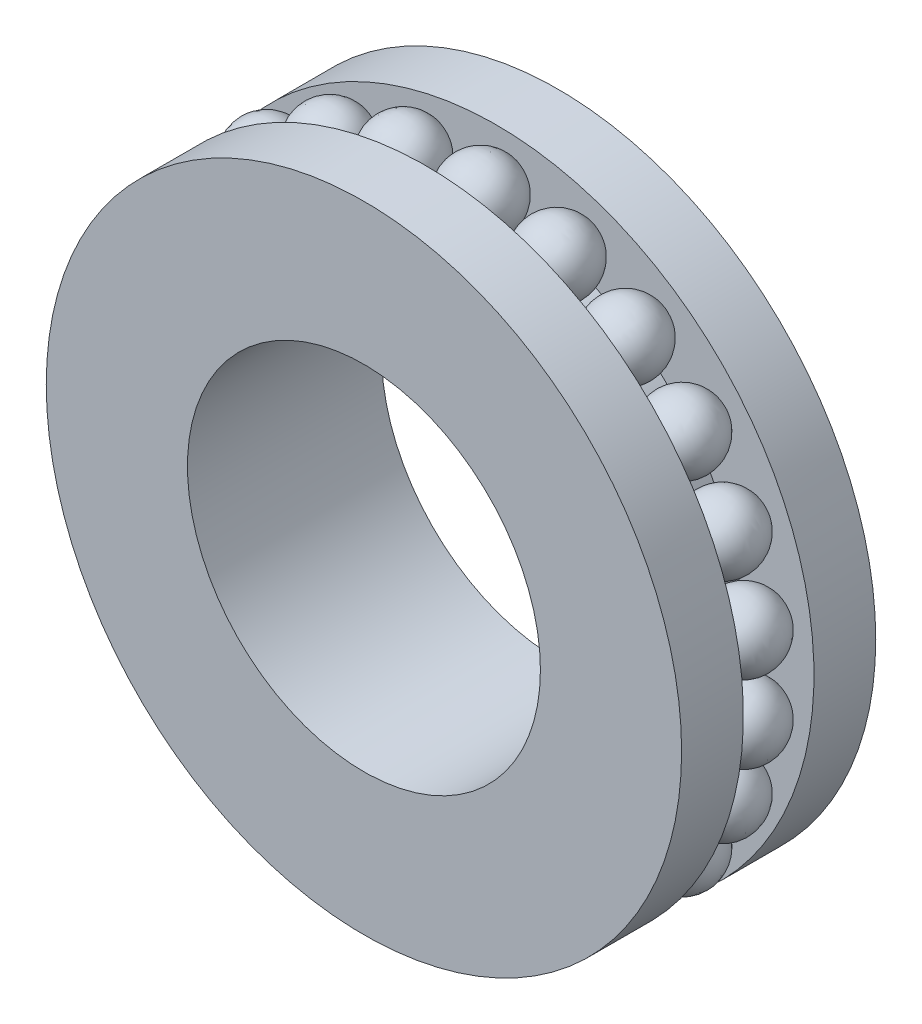
SolidWorks part; units mm, degrees
ref_plane "前视基准面" through (0, 0, 0) normal (0, 0, 1) x (1, 0, 0)
ref_plane "上视基准面" through (0, 0, 0) normal (0, 1, 0) x (1, 0, 0)
ref_plane "右视基准面" through (0, 0, 0) normal (1, 0, 0) x (0, 0, -1)
sketch "草图1" plane through (0, 0, 0) normal (0, 0, 1) x (1, 0, 0)
  circle A0 centre (0, 0) radius 5
  circle A1 centre (0, 0) radius 9
  dimension "D1" = 18
  dimension "D2" = 10
extrude "凸台-拉伸1" add sketch "草图1" along normal blind 5.5
ref_plane "基准面1" through (0, 0, 2.75) normal (0, 0, -1) x (-1, 0, 0)
sketch "草图2" plane through (0, 0, 2.75) normal (0, 0, -1) x (-1, 0, 0)
  circle A0 centre (0, 0) radius 9
  circle A1 centre (0, 0) radius 7
extrude "切除-拉伸1" cut sketch "草图2" against normal blind 1 and the other way blind 1
sketch "草图3" plane through (0, 0, 0) normal (0, 1, 0) x (1, 0, 0)
  line L0 (9.9, -2.75) -> (-9.9, -2.75) construction
  line L1 (-8.0736, -3.75) -> (-8.0736, -1.75) construction
  line L2 (-8.0736, -3.75) -> (-8.0736, -1.75)
  arc A0 (-8.0736, -1.75) -> (-8.0736, -3.75) centre (-8.0736, -2.75) ccw
revolve "旋转3" add sketch "草图3" angle 360 about L1
ref_axis "基准轴1" through (0, 0, 5.5) along (0, 0, -1)
pattern_circular "阵列(圆周)4" count 23 over 360 about axis through (0, 0, 5.5) along (0, 0, -1) of bodies 108
